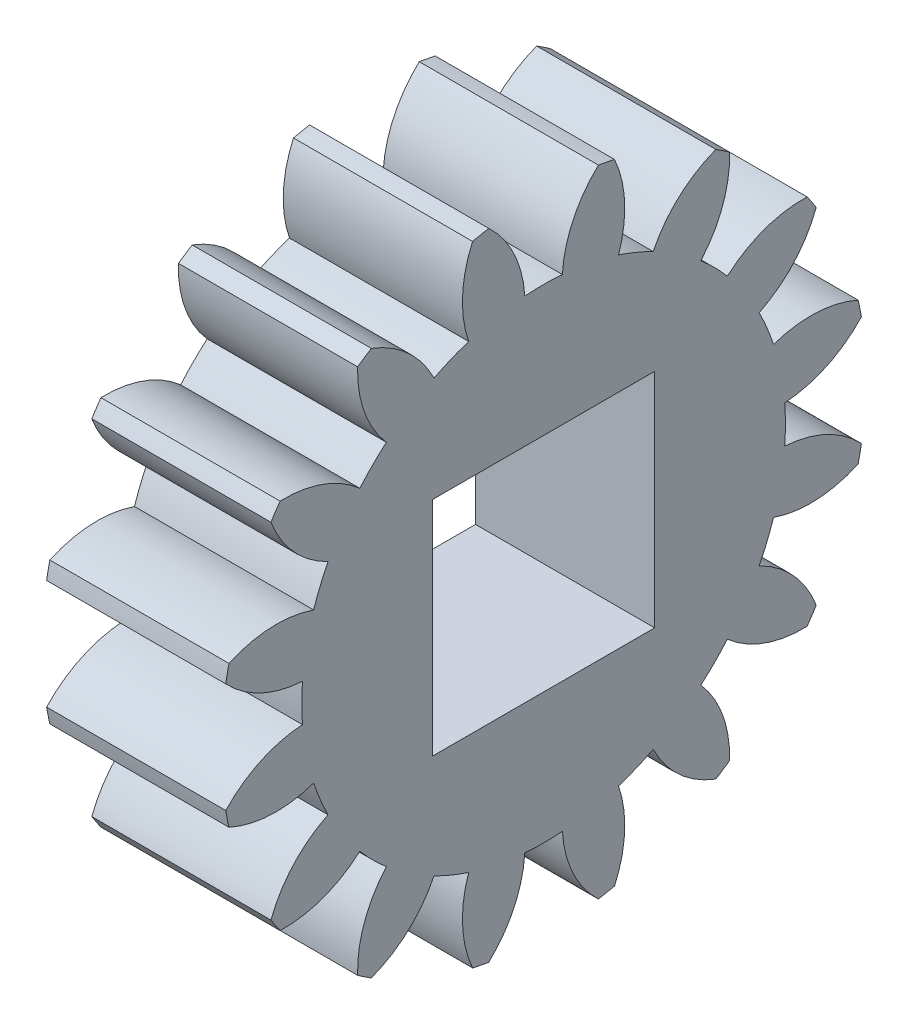
SolidWorks part; units mm, degrees
ref_plane "Plane1" through (0, 0, 0) normal (0, 0, 1) x (1, 0, 0)
ref_plane "Plane2" through (0, 0, 0) normal (0, 1, 0) x (1, 0, 0)
ref_plane "Plane3" through (0, 0, 0) normal (1, 0, 0) x (0, 0, -1)
sketch "HoldingSke" plane through (0, 0, 0) normal (0, 1, 0) x (1, 0, 0)
  line L0 (0, 0) -> (0.9613, -0.2756)
  line L1 (-15, 0) -> (100, 0) construction
  line L2 (0, 0) -> (-2.1039, 2.3779)
  line L3 (0, 0) -> (-11.863, 4.5341)
  line L4 (0, 0) -> (8.3015, 2.3804)
  line L5 (0, 0) -> (-46.8476, -17.4728)
  line L6 (0, 0) -> (-4.1448, -2.7965)
  line L7 (-2.1039, 2.3779) -> (8.6586, 51.2059)
  line L8 (-76.2, 54.61) -> (-75.2, 54.61)
  line L9 (-71.009, 38.7566) -> (-53.1078, 45.2721)
  line L10 (-76.2, 71.12) -> (104.1128, 71.12)
  line L11 (0, 0) -> (-5, 0)
  line L12 (-76.2, 101.6) -> (-76.162, 101.6)
  line L13 (24.9733, 27.94) -> (52.9518, 28.4284)
  line L14 (24.9733, 27.94) -> (24.9743, 27.94)
  line L15 (24.9733, 27.94) -> (100.4006, 29.5858)
  line L16 (-63.627, -1) -> (-12.827, -1)
  circle A0 centre (0, 0) radius 3
  circle A1 centre (0, 0) radius 6.749
  circle A2 centre (0, 0) radius 37.5
  circle A3 centre (0, 0) radius 3
  dimension "MHD" = 13.498
  dimension "Hub_dia" = 75
  dimension "Bore" = 6
  dimension "MBD" = 6
  dimension "Num_teeth" = 16
  dimension "Pitch_radius" = 180.3128
  dimension "Pitch" = 1
  dimension "Width" = 5
  dimension "Overall_len" = 50
  dimension "Show_teeth" = 16
  dimension "Thickness" = 5
  dimension "OAL" = 50.0001
  dimension "T_dim" = 1
  dimension "Ap" = 20
  dimension "H" = 19.05
  dimension "Backlash" = 0.038
  dimension "Addendum_fac" = 1
  dimension "Dedendum_fac" = 1.25
  dimension "Clearance_fac" = 0.25
  dimension "Dedendum_add" = 0.001
  dimension "Module" = 1
sketch "BasProSke" plane through (0, 0, 0) normal (0, 1, 0) x (1, 0, 0)
  line L0 (-10, 0) -> (60, 0) construction
  line L1 (0, 0) -> (0, 9)
  line L2 (0, 0) -> (5, 0)
  line L3 (5, 0) -> (5, 9)
  line L4 (5, 9) -> (0, 9)
  dimension "Diameter" = 18
  dimension "Thickness" = 5
revolve "Base-Revolve" add sketch "BasProSke" angle 360 about L0
sketch "TooCutSke" plane through (0, 0, 0) normal (1, 0, 0) x (0, 0, -1)
  line L1 (0, 0) -> (0, 107) construction
  line L2 (0, 0) -> (-0.8506, 7.9547) construction
  line L3 (0, 0) -> (-3.1089, 15.6293) construction
  line L4 (-0.8506, 7.9547) -> (-1.5544, 7.8146) construction
  arc A0 (0.5238, 6.7286) -> (-0.5238, 6.7286) centre (0, 0) ccw
  arc A1 (1.5534, 8.8907) -> (-1.5534, 8.8907) centre (0, 0) ccw
  circle A2 centre (0, 0) radius 8 construction
  circle A3 centre (0, 0) radius 7.5175 construction
  arc A4 (-0.5238, 6.7286) -> (-1.5534, 8.8907) centre (-3.7179, 6.5338) ccw
  arc A5 (1.5534, 8.8907) -> (0.5238, 6.7286) centre (3.7179, 6.5338) ccw
  dimension "Root_dia" = 13.498
  dimension "Overcut_dia" = 18.0508
  dimension "Pitch_dia" = 16
  dimension "Base_dia" = 15.0351
  dimension "Flank_rad" = 3.2
  dimension "Half_ang" = 11.25
  dimension "Half_CT" = 0.7176
extrude "ToothCut" cut sketch "TooCutSke" along normal through all
fillet "Breaks" [suppressed] radius 0.02 tangent propagation no
fillet "RootFillets" [suppressed] radius 0.251
pattern_circular "TeethCuts" count 16 every 22.5 about axis through (-10, 0, 0) along (1, 0, 0) of "ToothCut", "RootFillets", "Breaks"
sketch "HubNeaOneSke" plane through (0, 0, 0) normal (-1, 0, 0) x (0, 0, 1)
  circle A0 centre (0, 0) radius 6.749
  dimension "Diameter" = 13.498
extrude "HubNearOne" [suppressed] add sketch "HubNeaOneSke" along normal blind 45.0001
sketch "HubNeaBotSke" plane through (0, 0, 0) normal (-1, 0, 0) x (0, 0, 1)
  circle A0 centre (0, 0) radius 6.749
  dimension "Diameter" = 13.498
extrude "HubNearBoth" [suppressed] add sketch "HubNeaBotSke" along normal blind 22.5
ref_plane "FarPln" through (5, 0, 0) normal (1, 0, 0) x (0, 0, -1)
sketch "HubFarSke" plane through (5, 0, 0) normal (1, 0, 0) x (0, 0, -1)
  circle A0 centre (0, 0) radius 6.749
  dimension "Diameter" = 13.498
extrude "HubFar" [suppressed] add sketch "HubFarSke" along normal blind 22.5
sketch "BorSke" plane through (0, 0, 0) normal (1, 0, 0) x (0, 0, -1)
  circle A0 centre (0, 0) radius 3
  dimension "Diameter" = 6
extrude "Bore" cut sketch "BorSke" along normal mid plane 100.0001
sketch "KeySke" plane through (0, 0, 0) normal (1, 0, 0) x (0, 0, -1)
  line L0 (-1, 0) -> (-1, 4)
  line L1 (-1, 4) -> (1, 4)
  line L2 (1, 4) -> (1, 0)
  line L3 (0, 0) -> (0, 34) construction
  line L4 (-1, 0) -> (1, 0)
  dimension "Offset" = 4
  dimension "Width" = 2
extrude "Keyway" [suppressed] cut sketch "KeySke" along normal mid plane 100.0001
pattern_circular "Keyway2" [suppressed] count 2 every 90 about axis through (-10, 0, 0) along (1, 0, 0)
sketch "Sketch1" plane through (5, 0, 0) normal (1, 0, 0) x (0, 0, -1)
  line L1 (-3.1, -3.1) -> (3.1, -3.1)
  line L2 (-3.1, -3.1) -> (-3.1, 3.1)
  line L3 (-3.1, 3.1) -> (3.1, 3.1)
  line L4 (3.1, -3.1) -> (3.1, 3.1)
  line L5 (-3.1, -3.1) -> (3.1, 3.1) construction
  line L6 (-3.1, 3.1) -> (3.1, -3.1) construction
  circle A0 centre (0, 0) radius 3 construction
  point P0 (0, 0)
  dimension "D1" = 0
  dimension "D2" = 6.2
  dimension "D3" = 6.2
extrude "Cut-Extrude1" cut sketch "Sketch1" against normal blind 10
equation "' \"Module@HoldingSke\" = 6.35"
equation "' \"Num_teeth@HoldingSke\" = 12"
equation "' \"Ap@HoldingSke\" =  20"
equation "' \"Width@HoldingSke\" = 0.5 * 25.4"
equation "' \"Hub_dia@HoldingSke\"= 1 * 25.4"
equation "' \"Overall_len@HoldingSke\" = 1.0 * 25.4"
equation "' \"Bore@HoldingSke\" = 0.75 * 25.4"
equation "' \"T_dim@HoldingSke\" = 0.1 * 25.4"
equation "' \"Width@KeySke\" = 0.25 * 25.4"
equation "' \"Show_teeth@HoldingSke\" = 13"
equation "' \"Backlash@HoldingSke\" = 0.009 * 25.4"
equation "' \"Addendum_fac@HoldingSke\" = 1.0"
equation "' \"Dedendum_fac@HoldingSke\" = 1.25"
equation "' \"Dedendum_add@HoldingSke\" = 0.00005 * 25.4"
equation "' \"Clearance_fac@HoldingSke\" = 0.25"
equation "\"Pitch@HoldingSke\" = 1 / \"Module@HoldingSke\""
equation "\"Overcut_dia@TooCutSke\" = (\"Num_teeth@HoldingSke\" + 2 * \"Addendum_fac@HoldingSke\") / \"Pitch@HoldingSke\" + 0.002 * 25.4"
equation "\"Pitch_dia@TooCutSke\" = \"Num_teeth@HoldingSke\" / \"Pitch@HoldingSke\""
equation "\"Base_dia@TooCutSke\" = \"Num_teeth@HoldingSke\" / \"Pitch@HoldingSke\" * cos((\"Ap@HoldingSke\"  * 3.14159265 / 180))"
equation "\"Root_dia@TooCutSke\" = (\"Num_teeth@HoldingSke\" + 2) / \"Pitch@HoldingSke\" - 2 * (\"Addendum_fac@HoldingSke\" + \"Dedendum_fac@HoldingSke\") / \"Pitch@HoldingSke\" - \"Dedendum_add@HoldingSke\" * 2"
equation "\"Half_ang@TooCutSke\" = 180 / \"Num_teeth@HoldingSke\""
equation "\"Half_CT@TooCutSke\" = \"Num_teeth@HoldingSke\" / \"Pitch@HoldingSke\" * sin((3.14159265 / 2 / \"Num_teeth@HoldingSke\")) / 2 - 7 * \"Backlash@HoldingSke\" / 4"
equation "\"Flank_rad@TooCutSke\" = \"Num_teeth@HoldingSke\" / \"Pitch@HoldingSke\" / 5"
equation "\"Radius@RootFillets\" = \"Clearance_fac@HoldingSke\" / \"Pitch@HoldingSke\" + \"Dedendum_add@HoldingSke\""
equation "\"Break_rad@Breaks\" = 0.02 / \"Pitch@HoldingSke\""
equation "\"Thickness@HoldingSke\" = \"Width@HoldingSke\""
equation "\"OAL@HoldingSke\" = \"Thickness@HoldingSke\""
equation "\"MHD@HoldingSke\" = (\"Num_teeth@HoldingSke\" + 2) / \"Pitch@HoldingSke\" - 2 * (\"Addendum_fac@HoldingSke\" + \"Dedendum_fac@HoldingSke\")  / \"Pitch@HoldingSke\" - \"Dedendum_add@HoldingSke\" * 2"
equation "\"MBD@HoldingSke\" = (\"Num_teeth@HoldingSke\" + 2) / \"Pitch@HoldingSke\" - 2 * (\"Addendum_fac@HoldingSke\" + \"Dedendum_fac@HoldingSke\")  / \"Pitch@HoldingSke\" - \"Dedendum_add@HoldingSke\" * 2 - 0.002 * 25.4"
equation "\"MHD@HoldingSke\" = ((sgn( \"MHD@HoldingSke\" - \"Hub_dia@HoldingSke\" )-1)*( \"MHD@HoldingSke\" - \"Hub_dia@HoldingSke\" ))/-2+ \"Hub_dia@HoldingSke\""
equation "\"MBD@HoldingSke\" = ((sgn( \"MBD@HoldingSke\" - \"Bore@HoldingSke\" )-1)*( \"MBD@HoldingSke\" - \"Bore@HoldingSke\" ))/-2+ \"Bore@HoldingSke\""
equation "\"OAL@HoldingSke\" = ((sgn( \"OAL@HoldingSke\" - \"Overall_len@HoldingSke\" )+1)*( \"OAL@HoldingSke\" - \"Overall_len@HoldingSke\" ))/2 + \"Overall_len@HoldingSke\" + 0.000002 * 25.4"
equation "\"Num_teeth@TeethCuts\" = int( \"Show_teeth@HoldingSke\" ) + 1"
equation "\"Num_teeth@TeethCuts\" = ((sgn( \"Num_teeth@TeethCuts\" - \"Num_teeth@HoldingSke\" )-1)*( \"Num_teeth@TeethCuts\" - \"Num_teeth@HoldingSke\" ))/-2+ \"Num_teeth@HoldingSke\""
equation "\"Num_teeth@TeethCuts\" = ((sgn( \"Num_teeth@TeethCuts\" - 2.0)+1)*( \"Num_teeth@TeethCuts\" - 2.0))/2 +2.0"
equation "\"Angle@TeethCuts\" = 360.0 / \"Num_teeth@HoldingSke\""
equation "\"Diameter@BasProSke\" = (\"Num_teeth@HoldingSke\" + 2 * \"Addendum_fac@HoldingSke\") / \"Pitch@HoldingSke\""
equation "\"Thickness@BasProSke\"  = \"Thickness@HoldingSke\""
equation "' \"Fillet_rad@BasProSke\" =  \"Thickness@HoldingSke\" * 0.05"
equation "\"MHD@HoldingSke\" = ((sgn( \"MHD@HoldingSke\" - \"Root_dia@TooCutSke\" )-1)*( \"MHD@HoldingSke\" - \"Root_dia@TooCutSke\" ))/-2+ \"Root_dia@TooCutSke\""
equation "\"Diameter@HubNeaOneSke\" = \"MHD@HoldingSke\""
equation "\"Length@HubNearOne\" = \"OAL@HoldingSke\" - \"Thickness@BasProSke\""
equation "\"Diameter@HubNeaBotSke\" = \"MHD@HoldingSke\""
equation "\"Length@HubNearBoth\" = ( \"OAL@HoldingSke\" - \"Thickness@BasProSke\" ) / 2.0"
equation "\"Thickness@FarPln\" = \"Thickness@BasProSke\""
equation "\"Diameter@HubFarSke\" = \"MHD@HoldingSke\""
equation "\"Length@HubFar\" = ( \"OAL@HoldingSke\" - \"Thickness@BasProSke\" ) / 2.0"
equation "\"Diameter@BorSke\" = \"MBD@HoldingSke\""
equation "\"D1@Bore\" = \"OAL@HoldingSke\" * 2.0"
equation "\"D1@Keyway\" = \"OAL@HoldingSke\" * 2.0"
equation "\"Offset@KeySke\" = \"T_dim@HoldingSke\" + \"MBD@HoldingSke\" / 2.0"
